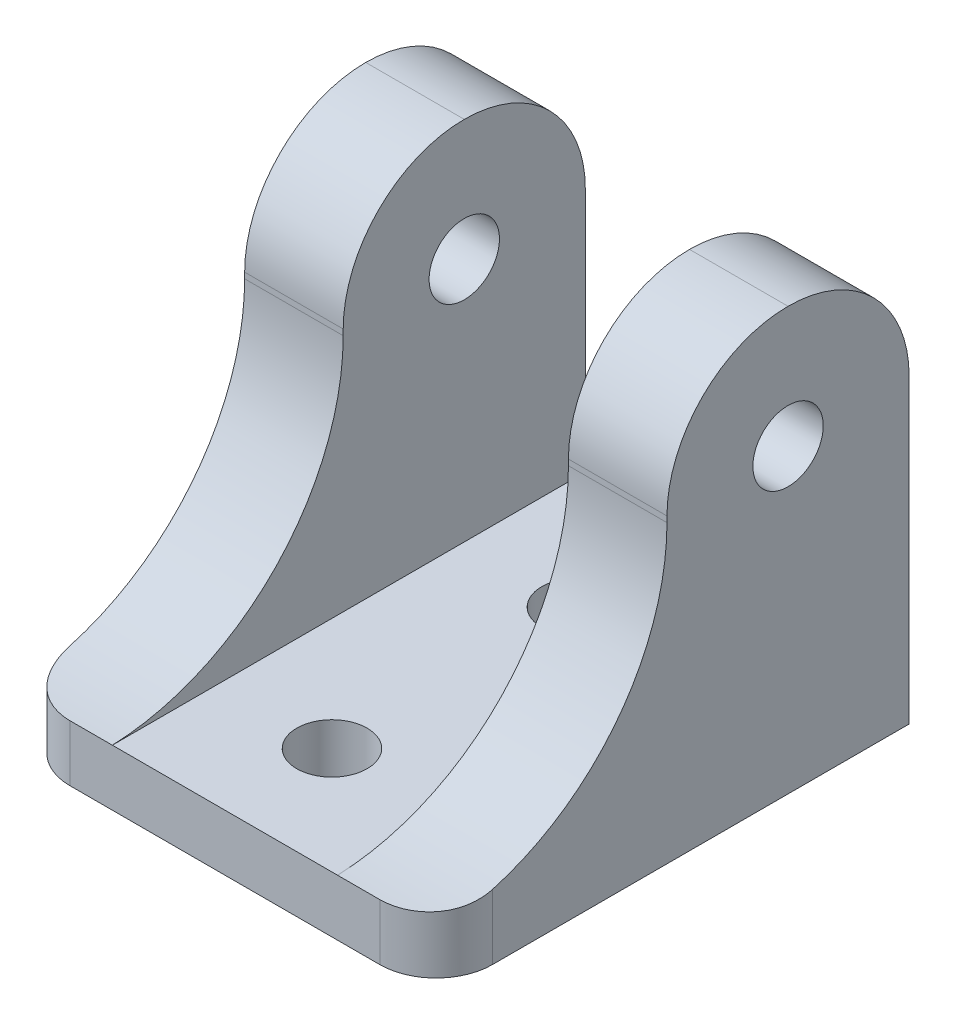
SolidWorks part; units mm, degrees
ref_plane "Front Plane" through (0, 0, 0) normal (0, 0, 1) x (1, 0, 0)
ref_plane "Top Plane" through (0, 0, 0) normal (0, 1, 0) x (1, 0, 0)
ref_plane "Right Plane" through (0, 0, 0) normal (1, 0, 0) x (0, 0, -1)
sketch "Sketch1" plane through (0, 0, 0) normal (0, 1, 0) x (1, 0, 0)
  line L1 (-17.3979, 19.0662) -> (20.7021, 19.0662)
  line L2 (-17.3979, 19.0662) -> (-17.3979, -23.6058)
  line L3 (-17.3979, -23.6058) -> (20.7021, -23.6058)
  line L4 (20.7021, 19.0662) -> (20.7021, -23.6058)
  dimension "D1" = 38.1
  dimension "D2" = 42.672
extrude "Boss-Extrude1" add sketch "Sketch1" along normal blind 5.08
sketch "Sketch2" plane through (0, 5.08, 0) normal (0, 1, 0) x (1, 0, 0)
  line L1 (20.7021, 19.0662) -> (11.8121, 19.0662)
  line L2 (20.7021, 19.0662) -> (20.7021, -2.7778)
  line L3 (20.7021, -2.7778) -> (11.8121, -2.7778)
  line L4 (11.8121, 19.0662) -> (11.8121, -2.7778)
  line L5 (-17.3979, 19.0662) -> (-8.5079, 19.0662)
  line L6 (-17.3979, 19.0662) -> (-17.3979, -2.7778)
  line L7 (-17.3979, -2.7778) -> (-8.5079, -2.7778)
  line L8 (-8.5079, 19.0662) -> (-8.5079, -2.7778)
  dimension "D1" = 8.89
  dimension "D2" = 21.844
extrude "Boss-Extrude2" add sketch "Sketch2" along normal blind 33.02
fillet "Fillet1" radius 10.922 4 edges at (-12.9529, 38.1, -19.0662) (16.2571, 38.1, -19.0662) (16.2571, 38.1, 2.7778) (-12.9529, 38.1, 2.7778)
fillet "Fillet2" radius 21.59 2 edges at (-12.9529, 5.08, 2.7778)
fillet "Fillet3" radius 5.08 2 edges at (-17.3979, 2.54, 23.6058) (20.7021, 2.54, 23.6058)
hole_wizard "1 (1) Diameter Hole1" positions "3DSketch1" profile "Sketch4" hole size "1" standard "ANSI Inch"
sketch3d "3DSketch1"
  line L1 (11.8121, 5.08, -19.0662) -> (-8.5079, 5.08, -19.0662) construction
  line L2 (1.6521, 5.08, 23.6058) -> (1.6521, 5.08, -19.0662)
  line L3 (-8.5079, 5.08, 23.6058) -> (11.8121, 5.08, 23.6058) construction
  line L5 (20.7021, 27.178, -19.0662) -> (20.7021, 0, -19.0662) construction
  point P0 (1.6521, 5.08, 13.9538)
  point P2 (1.6521, 5.08, -8.1442)
  point P17 (20.7021, 27.178, -8.1442)
  dimension "D1" = 33.02
  dimension "D3" = 27.178
  dimension "D2" = 10.922
  dimension "D4" = 10.922
sketch "Sketch4" plane through (1.6521, 5.08, 13.9538) normal (1, 0, 0) x (0, 0, 1)
  line L0 (0, 0) -> (0, 52.7077)
  line L1 (0, 52.7077) -> (3.175, 50.8)
  line L2 (3.175, 50.8) -> (3.175, 0)
  line L5 (3.175, 0) -> (0, 0)
  line L10 (0, 52.7077) -> (-3.175, 50.8) construction
  line L11 (0, -6.35) -> (0, 107.95) construction
  dimension "Hole Dia." = 6.35
  dimension "Hole Depth" = 50.8
  dimension "Drill Angle" = 118
